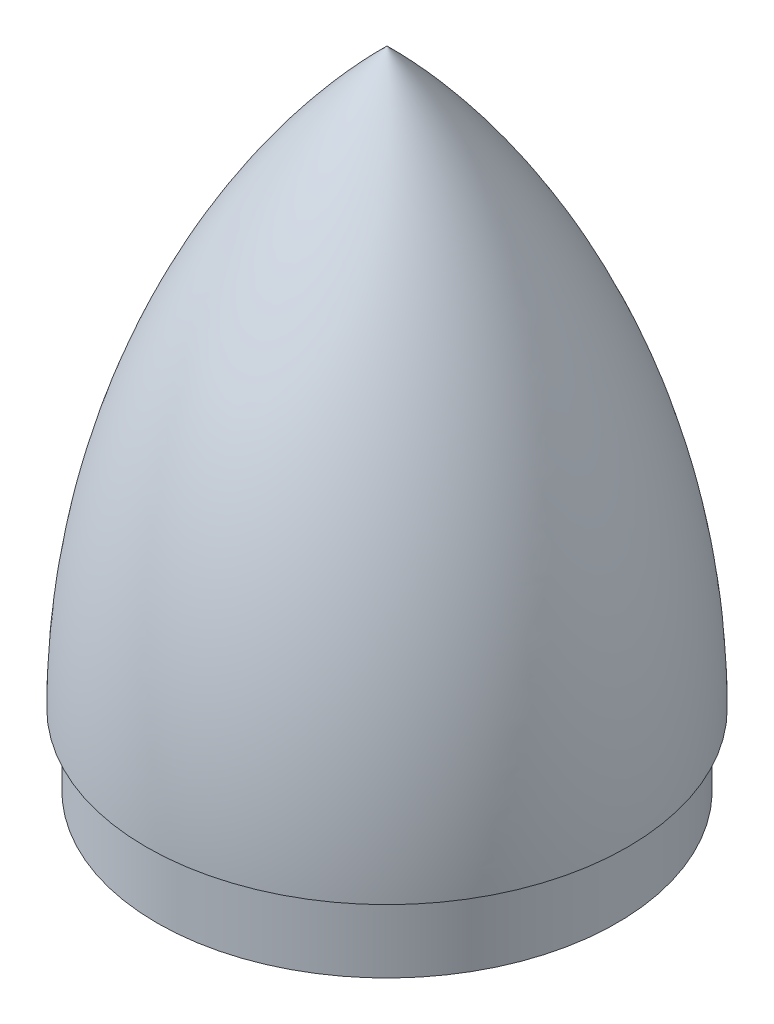
SolidWorks part; units mm, degrees
ref_plane "Front Plane" through (0, 0, 0) normal (1, 0, 0) x (0, 1, 0)
ref_plane "Top Plane" through (0, 0, 0) normal (0, 0, 1) x (0, 1, 0)
ref_plane "Right Plane" through (0, 0, 0) normal (0, 1, 0) x (-1, 0, 0)
sketch "Sketch1" plane through (0, 0, 0) normal (0, 0, 1) x (0, 1, 0)
  line L1 (0, 41.1) -> (12.7, 41.1)
  line L2 (12.7, 41.1) -> (12.7, 43)
  line L4 (0, 40.1) -> (13.7, 40.1)
  line L7 (115.2, 0) -> (113.7936, 0)
  line L8 (-1000, 0) -> (49000, 0) construction
  line L9 (13.7, 40.1) -> (35.906, 40.1)
  line L10 (-0.0805, 41.0968) -> (-0.2014, 41.1) construction
  line L11 (13.7, 40.1) -> (13.7, 41.9965) construction
  line L12 (0, 40.1) -> (0, 40.1) construction
  line L13 (0, 40.1) -> (0, 41.1)
  line L14 (-0.2014, 41.1) -> (12.7, 41.1) construction
  arc A0 (12.7, 43) -> (115.2, 0) centre (12.7, -100.6657) cw
  arc A1 (35.906, 40.1) -> (113.7936, 0) centre (12.7, -100.6657) cw
  arc A2 (13.7, 41.9965) -> (114.4865, -0.7007) centre (12.7, -100.6657) cw construction
  dimension "D1" = 86
  dimension "D2" = 1
  dimension "D3" = 82.2
  dimension "D4" = 12.7
  dimension "D5" = 102.5
revolve "Revolve1" add sketch "Sketch1" angle 360 about L8
